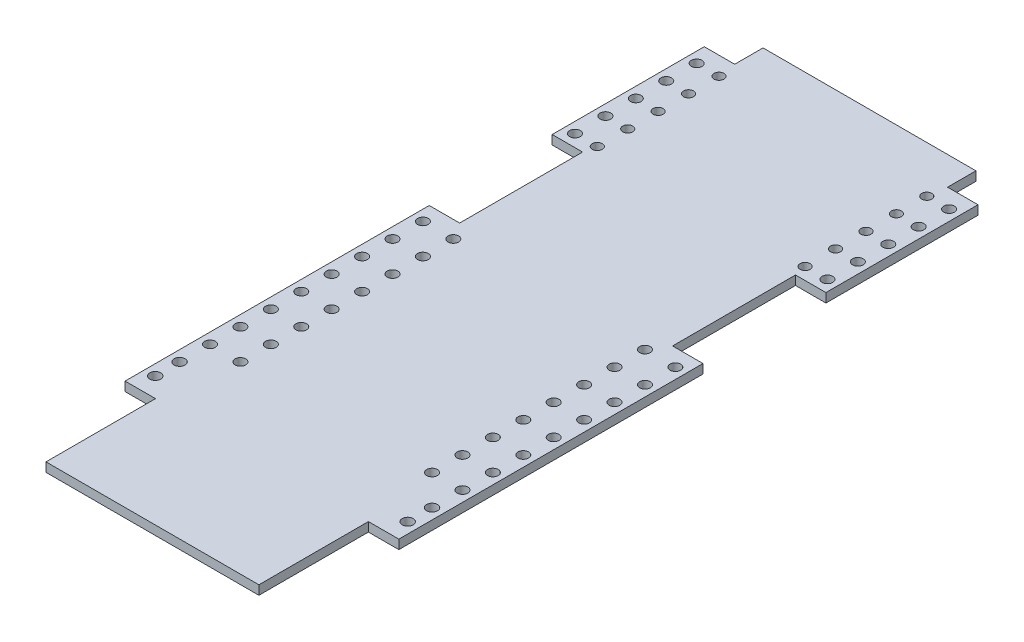
SolidWorks part; units mm, degrees
ref_plane "Front Plane" through (0, 0, 0) normal (0, 0, 1) x (1, 0, 0)
ref_plane "Top Plane" through (0, 0, 0) normal (0, 1, 0) x (1, 0, 0)
ref_plane "Right Plane" through (0, 0, 0) normal (1, 0, 0) x (0, 0, -1)
sketch "Sketch5" plane through (0, 0, 0) normal (0, 1, 0) x (1, 0, 0)
  line L0 (70, 36) -> (80, 36)
  line L1 (0, 0) -> (70, 0)
  line L2 (0, 0) -> (0, 235.74)
  line L3 (0, 235.74) -> (70, 235.74)
  line L4 (70, 0) -> (70, 235.74)
  line L5 (80, 36) -> (80, 136)
  line L6 (80, 136) -> (70, 136)
  line L7 (35, 235.74) -> (35, 0) construction
  line L8 (-10, 136) -> (0, 136)
  line L9 (-10, 36) -> (-10, 136)
  line L10 (0, 36) -> (-10, 36)
  dimension "D1" = 235.74
  dimension "D2" = 70
  dimension "D3" = 36
  dimension "D4" = 100
  dimension "D5" = 10
extrude "Boss-Extrude5" add sketch "Sketch5" along normal blind 3 contours L10 L2 L8 L9 | L7 L3 L2 L1 | L3 L7 L1 L4 | L5 L6 L4 L0 region at (75, 0, -86) region at (52.5, 0, -117.87) region at (17.5, 0, -117.87) region at (-5, 0, -86)
sketch "Sketch6" plane through (0, 3, 0) normal (0, 1, 0) x (1, 0, 0)
  point P0 (76.5, 50.4206)
  point P3 (76.5, 42.4206)
hole_wizard "M3 Clearance Hole1" positions "Sketch6" profile "Sketch7" hole size "M3" standard "ANSI Metric" end condition through all
sketch "Sketch7" plane through (76.5, 3, -50.4206) normal (1, 0, 0) x (0, 0, 1)
  line L0 (0, 0) -> (0, 3)
  line L1 (0, 3) -> (1.8, 3)
  line L2 (1.8, 3) -> (1.8, 0)
  line L5 (1.8, 0) -> (0, 0)
  line L11 (0, -6.35) -> (0, 107.95) construction
  dimension "Thru Hole Dia." = 3.6
  dimension "Thru Hole Depth" = 3
ref_plane "Plane1" through (35, 0, 0) normal (-1, 0, 0) x (0, 0, 1)
sketch "Sketch8" plane through (0, 3, 0) normal (0, 1, 0) x (1, 0, 0)
  line L0 (80, 36) -> (80, 136) construction
  circle A0 centre (76.5, 60.4206) radius 1.75
  circle A4 centre (76.5, 50.4206) radius 1.8 construction
  circle A6 centre (66.5, 60.4206) radius 1.75
  circle A7 centre (66.5, 70.4206) radius 1.75
  circle A8 centre (66.5, 80.4206) radius 1.75
  circle A9 centre (66.5, 90.4206) radius 1.75
  circle A10 centre (66.5, 100.4206) radius 1.75
  circle A11 centre (66.5, 110.4206) radius 1.75
  circle A12 centre (66.5, 120.4206) radius 1.75
  circle A13 centre (66.5, 130.4206) radius 1.75
  circle A14 centre (76.5, 70.4206) radius 1.75
  circle A15 centre (76.5, 80.4206) radius 1.75
  circle A16 centre (76.5, 90.4206) radius 1.75
  circle A17 centre (76.5, 100.4206) radius 1.75
  circle A18 centre (76.5, 110.4206) radius 1.75
  circle A19 centre (76.5, 120.4206) radius 1.75
  circle A20 centre (76.5, 130.4206) radius 1.75
  dimension "D1" = 3.5
  dimension "D3" = 10
  dimension "D2" = 3.5
  dimension "D4" = 2
  dimension "D5" = 8
extrude "Cut-Extrude1" cut sketch "Sketch8" against normal through all
sketch "Sketch10" plane through (0, 0, 0) normal (0, -1, 0) x (1, 0, 0)
  line L0 (70, -176.4206) -> (80, -176.4206)
  line L1 (70, -136) -> (70, -235.74) construction
  line L2 (80, -176.4206) -> (80, -226.4206)
  line L3 (80, -226.4206) -> (70, -226.4206)
  line L4 (70, -226.4206) -> (70, -176.4206)
  circle A0 centre (76.5, -180.4206) radius 1.75
  circle A4 centre (76.5, -130.4206) radius 1.75 construction
  circle A5 centre (76.5, -190.4206) radius 1.75
  circle A8 centre (76.5, -200.4206) radius 1.75
  circle A9 centre (76.5, -210.4206) radius 1.75
  circle A10 centre (76.5, -220.4206) radius 1.75
  dimension "D8" = 3.5
  dimension "D11" = 3.5
  dimension "D3" = 50
  dimension "D1" = 10
  dimension "D2" = 50
  dimension "D4" = 5
  dimension "D7" = 4
extrude "Boss-Extrude6" add sketch "Sketch10" against normal blind 3
sketch "Sketch11" plane through (0, 3, 0) normal (0, 1, 0) x (1, 0, 0)
  circle A13 centre (76.5, 180.4206) radius 1.75 construction
  circle A14 centre (76.5, 180.4206) radius 1.75 construction
  circle A15 centre (69.1652, 180.4206) radius 1.65
  circle A16 centre (69.1652, 190.4206) radius 1.65
  circle A17 centre (69.1652, 200.4206) radius 1.65
  circle A18 centre (69.1652, 210.4206) radius 1.65
  circle A19 centre (69.1652, 220.4206) radius 1.65
  dimension "D1" = 3.3
  dimension "D2" = 5
extrude "Cut-Extrude2" cut sketch "Sketch11" against normal through all
mirror "Mirror1" about plane through (35, 0, 0) normal (-1, 0, 0) of "Cut-Extrude2", "Boss-Extrude6", "M3 Clearance Hole1", "Cut-Extrude1"
equation "\"Spacing\"=8"
